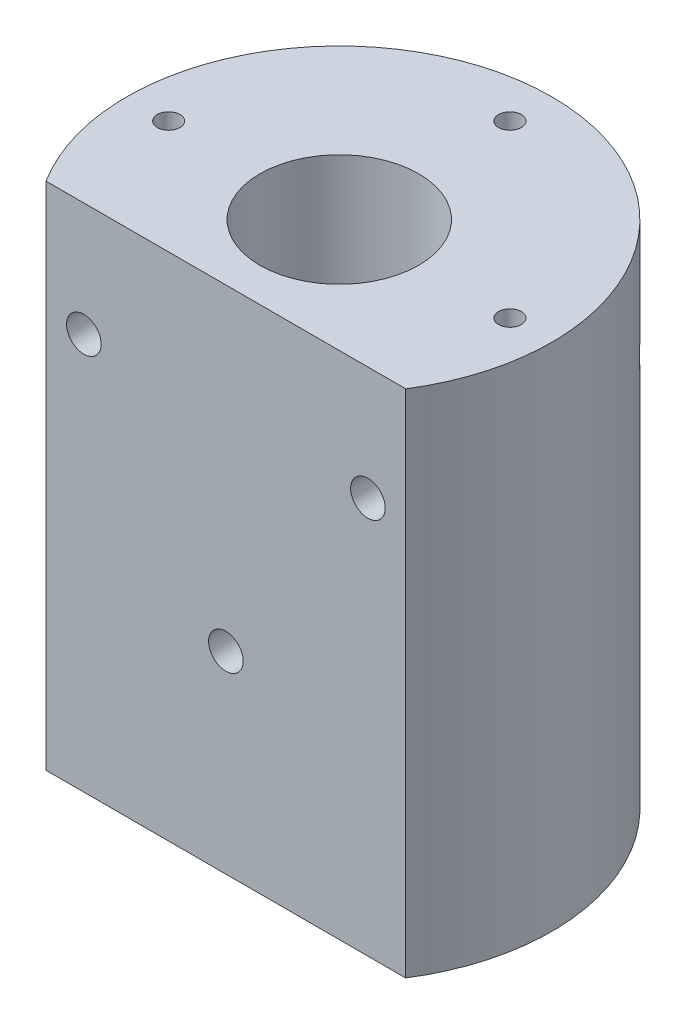
SolidWorks part; units mm, degrees
ref_plane "Front Plane" through (0, 0, 0) normal (0, 0, 1) x (1, 0, 0)
ref_plane "Top Plane" through (0, 0, 0) normal (0, 1, 0) x (1, 0, 0)
ref_plane "Right Plane" through (0, 0, 0) normal (1, 0, 0) x (0, 0, -1)
sketch "Sketch1" plane through (0, 0, 0) normal (0, 1, 0) x (1, 0, 0)
  line L0 (-31.7214, -20) -> (31.7214, -20)
  line L1 (0, -14) -> (0, -20) construction
  line L2 (-32.1, 0) -> (32.1, 0) construction
  circle A0 centre (0, 0) radius 14
  circle A1 centre (0, 0) radius 37.5
  circle A2 centre (0, 0) radius 30.1 construction
  circle A3 centre (-30.1, 0) radius 2
  circle A4 centre (30.1, 0) radius 2
  circle A5 centre (0, 30.1) radius 2
  circle A6 centre (0, 0) radius 11.2
  dimension "D1" = 28
  dimension "D2" = 75
  dimension "D4" = 4
  dimension "D5" = 22.4
  dimension "D3" = 6
  dimension "D6" = 64.2
extrude "Boss-Extrude1" add sketch "Sketch1" against normal blind 90 contours L0 A1 A5 A4 A3 A0 | A0 A6 | A3 | A5 | A4 region at (-10.1467, 0, -35.1185) region at (-13.604, 0, 0) region at (-30.1, 0, 0) region at (30.1, 0, 0) region at (0, 0, -30.1)
extrude "Corte-extrusão1" cut sketch "Sketch1<3>" against normal blind 14.6 contours A3 | A5 | A4 region at (-30.1, 0, 0) region at (30.1, 0, 0) region at (0, 0, -30.1)
sketch "Sketch1<3>" plane through (0, 0, 0) normal (0, 1, 0) x (1, 0, 0) same geometry as "Sketch1"
extrude "Corte-extrusão2" cut sketch "Sketch1<4>" against normal blind 50 contours A0 A6 region at (-13.604, 0, 0)
sketch "Sketch1<4>" plane through (0, 0, 0) normal (0, 1, 0) x (1, 0, 0) same geometry as "Sketch1"
sketch "Esboço1" plane through (0, -90, 0) normal (0, -1, 0) x (1, 0, 0)
  line L0 (-27.5, 0) -> (27.5, 0) construction
  circle A0 centre (-25, 0) radius 2.5
  circle A1 centre (25, 0) radius 2.5
  point P6 (-22.9396, 0)
  point P7 (23.4474, 0)
  point P8 (17.3072, -3.8199)
  point P9 (0, 0)
  dimension "D1" = 5
  dimension "D2" = 55
extrude "Corte-extrusão3" cut sketch "Esboço1" against normal blind 23
sketch "Esboço2" plane through (0, 0, 20) normal (0, 0, 1) x (1, 0, 0)
  line L0 (-28.1, -20.05) -> (28.1, -20.05) construction
  line L1 (0, -20.05) -> (0, 0) construction
  line L2 (25.05, -17) -> (25.05, 0) construction
  line L3 (-31.7214, 0) -> (31.7214, 0) construction
  line L4 (0, -90) -> (0, -59)
  line L5 (-31.7214, -90) -> (31.7214, -90) construction
  circle A0 centre (-25.05, -20.05) radius 3.05
  circle A1 centre (25.05, -20.05) radius 3.05
  circle A2 centre (0, -55.95) radius 3.05
  dimension "D1" = 6.1
  dimension "D2" = 56.2
  dimension "D3" = 17
  dimension "D4" = 31
extrude "Corte-extrusão4" cut sketch "Esboço2" against normal through all contours A1 | A0 region at (-25.05, -20.05, 20) region at (25.05, -20.05, 20)
extrude "Corte-extrusão5" cut sketch "Esboço2<3>" against normal up to next contours A2 region at (0, -55.95, 20)
sketch "Esboço2<3>" plane through (0, 0, 20) normal (0, 0, 1) x (1, 0, 0) same geometry as "Esboço2"
